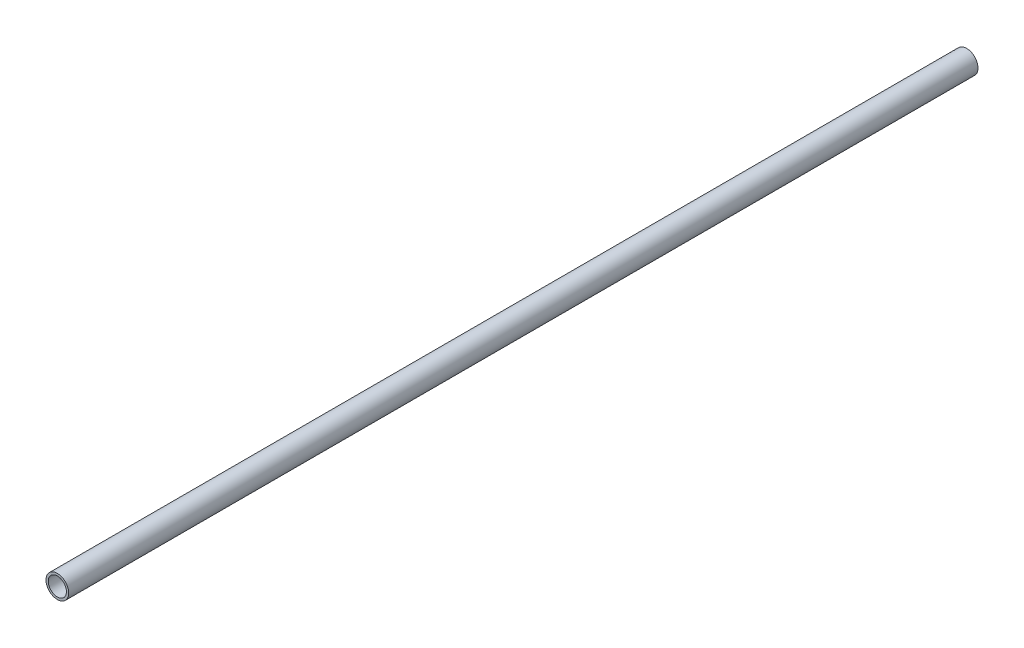
SolidWorks part; units mm, degrees
material "1060 Alloy"
ref_plane "Front Plane" through (0, 0, 0) normal (0, 0, 1) x (1, 0, 0)
ref_plane "Top Plane" through (0, 0, 0) normal (0, 1, 0) x (1, 0, 0)
ref_plane "Right Plane" through (0, 0, 0) normal (1, 0, 0) x (0, 0, -1)
sketch "Sketch1" plane through (0, 0, 0) normal (0, 0, 1) x (1, 0, 0)
  circle A0 centre (0, 0) radius 5
  circle A1 centre (0, 0) radius 4
  dimension "1" = 10
  dimension "D2" = 8
extrude "body" add sketch "Sketch1" along normal blind 400
